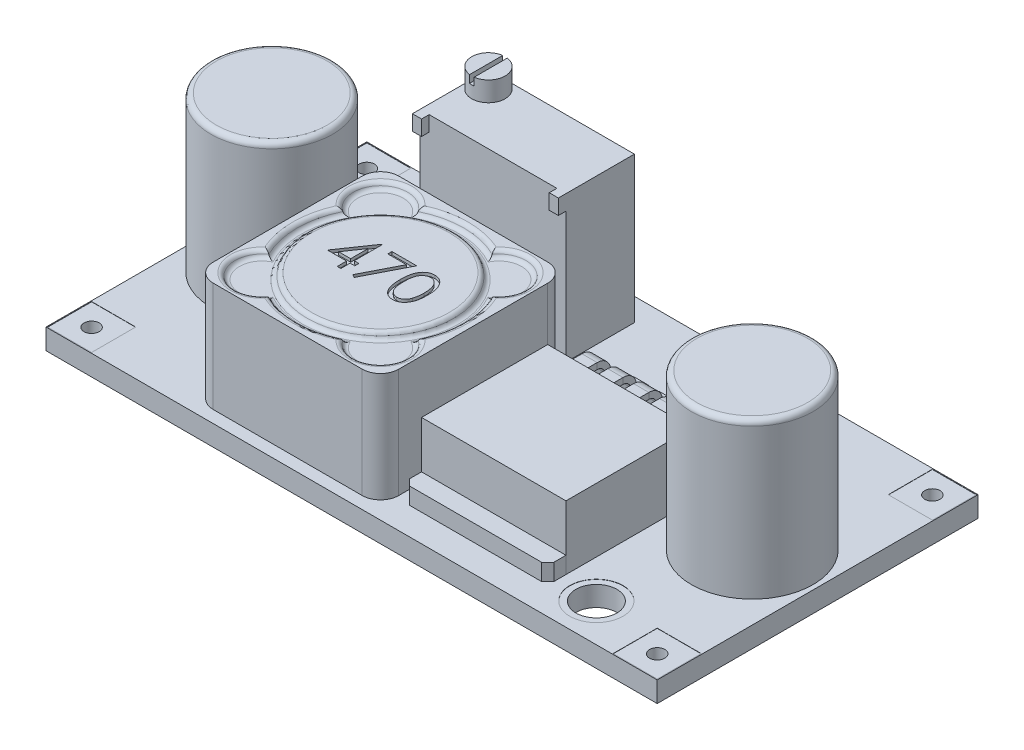
SolidWorks part; units mm, degrees
ref_plane "Front Plane" through (0, 0, 0) normal (0, 0, 1) x (1, 0, 0)
ref_plane "Top Plane" through (0, 0, 0) normal (0, 1, 0) x (1, 0, 0)
ref_plane "Right Plane" through (0, 0, 0) normal (1, 0, 0) x (0, 0, -1)
sketch "Sketch1" plane through (0, 0, 0) normal (0, 1, 0) x (1, 0, 0)
  line L0 (-20.1, 10.55) -> (-18.6, 9.05) construction
  line L1 (-20.1, -10.55) -> (20.1, -10.55)
  line L2 (-20.1, -10.55) -> (-20.1, 10.55)
  line L3 (-20.1, 10.55) -> (20.1, 10.55)
  line L4 (20.1, -10.55) -> (20.1, 10.55)
  line L5 (-20.1, -10.55) -> (20.1, 10.55) construction
  line L6 (-20.1, 10.55) -> (20.1, -10.55) construction
  line L7 (0, 0) -> (0, 10.55) construction
  line L8 (0, 0) -> (-20.1, 0) construction
  line L9 (-13.6, 8.05) -> (-13.6, 10.55) construction
  line L10 (-13.6, 8.05) -> (-20.1, 8.05) construction
  line L11 (20.1, -8.05) -> (13.6, -8.05) construction
  line L12 (13.6, -8.05) -> (13.6, -10.55) construction
  circle A0 centre (-18.6, 9.05) radius 0.5
  circle A1 centre (18.6, 9.05) radius 0.5
  circle A2 centre (18.6, -9.05) radius 0.5
  circle A3 centre (-18.6, -9.05) radius 0.5
  circle A4 centre (-13.6, 8.05) radius 1.35
  circle A5 centre (13.6, -8.05) radius 1.35
  point P0 (0, 0)
  dimension "D5" = 1
  dimension "D6" = 2.7
  dimension "D1" = 21.1
  dimension "D2" = 40.2
  dimension "D3" = 45
  dimension "D4" = 1.5
  dimension "D7" = 6.5
  dimension "D8" = 2.5
extrude "Boss-Extrude1" add sketch "Sketch1" along normal blind 1.35
sketch "Sketch3" plane through (0, 1.35, 0) normal (0, 1, 0) x (1, 0, 0)
  line L1 (-20.1, 10.55) -> (-20.1, -10.55) construction
  circle A0 centre (-15.8, 0) radius 4
  dimension "D1" = 4.3
  dimension "D2" = 8
extrude "Boss-Extrude2" add sketch "Sketch3" along normal blind 10.2
mirror "Mirror6" about plane through (0, 0, 0) normal (1, 0, 0) of "Boss-Extrude2"
sketch "Sketch4" plane through (0, 1.35, 0) normal (0, 1, 0) x (1, 0, 0)
  line L0 (20.1, 10.55) -> (-20.1, 10.55) construction
  line L1 (-10.6, 9.05) -> (-1, 9.05)
  line L2 (-10.6, 9.05) -> (-10.6, 4.55)
  line L3 (-10.6, 4.55) -> (-1, 4.55)
  line L4 (-1, 9.05) -> (-1, 4.55)
  line L5 (-20.1, 10.55) -> (-20.1, -10.55) construction
  dimension "D1" = 4.5
  dimension "D2" = 9.6
  dimension "D3" = 1.5
  dimension "D4" = 9.5
extrude "Boss-Extrude3" add sketch "Sketch4" along normal blind 9.6
sketch "Sketch5" plane through (0, 1.35, 0) normal (0, 1, 0) x (1, 0, 0)
  line L0 (-20.1, -10.55) -> (20.1, -10.55) construction
  line L1 (-9.9, 2.45) -> (-0.1, 2.45)
  line L2 (-11.1, 1.25) -> (-11.1, -8.55)
  line L3 (-9.9, -9.75) -> (-0.1, -9.75)
  line L4 (1.1, 1.25) -> (1.1, -8.55)
  line L5 (-20.1, 10.55) -> (-20.1, -10.55) construction
  arc A0 (-0.1, 2.45) -> (1.1, 1.25) centre (-0.1, 1.25) cw
  arc A1 (-0.1, -9.75) -> (1.1, -8.55) centre (-0.1, -8.55) ccw
  arc A2 (-11.1, -8.55) -> (-9.9, -9.75) centre (-9.9, -8.55) ccw
  arc A3 (-9.9, 2.45) -> (-11.1, 1.25) centre (-9.9, 1.25) ccw
  point P10 (1.1, 2.45)
  point P15 (-11.1, -9.75)
  point P18 (-11.1, 2.45)
  dimension "D5" = 1.2
  dimension "D1" = 12.2
  dimension "D2" = 12.2
  dimension "D3" = 0.8
  dimension "D4" = 9
extrude "Boss-Extrude4" add sketch "Sketch5" along normal blind 7.2
sketch "Sketch6" plane through (0, 1.35, 0) normal (0, 1, 0) x (1, 0, 0)
  line L0 (1.1, -8.55) -> (1.1, 1.25) construction
  line L1 (1.6, -7.55) -> (11.1, -7.55)
  line L2 (1.6, -7.55) -> (1.6, 0.75)
  line L3 (1.6, 0.75) -> (11.1, 0.75)
  line L4 (11.1, -7.55) -> (11.1, 0.75)
  line L5 (-20.1, -10.55) -> (20.1, -10.55) construction
  dimension "D1" = 9.5
  dimension "D2" = 0.5
  dimension "D3" = 8.3
  dimension "D4" = 3
extrude "Boss-Extrude5" add sketch "Sketch6" along normal blind 4.2
sketch "Sketch7" plane through (0, 1.35, 0) normal (0, 1, 0) x (1, 0, 0)
  line L1 (-20.05, 7.6) -> (-17.15, 7.6)
  line L2 (-20.05, 7.6) -> (-20.05, 10.5)
  line L3 (-20.05, 10.5) -> (-17.15, 10.5)
  line L4 (-17.15, 7.6) -> (-17.15, 10.5)
  line L5 (-20.05, 7.6) -> (-17.15, 10.5) construction
  line L6 (-20.05, 10.5) -> (-17.15, 7.6) construction
  circle A0 centre (-18.6, 9.05) radius 0.5 construction
  circle A1 centre (-18.6, 9.05) radius 0.5
  point P0 (-18.6, 9.05)
  dimension "D1" = 2.9
extrude "Cut-Extrude1" cut sketch "Sketch7" against normal blind 0.015
ref_plane "Plane1" through (0, 0.675, 0) normal (0, 1, 0) x (1, 0, 0)
mirror "Mirror7" about plane through (0, 0, 0) normal (1, 0, 0) of "Cut-Extrude1"
mirror "Mirror8" about plane through (0, 0, 0) normal (0, 0, 1) of "Mirror7", "Cut-Extrude1"
mirror "Mirror9" about plane through (0, 0.675, 0) normal (0, 1, 0) of "Mirror8", "Cut-Extrude1", "Mirror7"
sketch "Sketch8" plane through (0, 10.95, 0) normal (0, 1, 0) x (1, 0, 0)
  line L0 (-1, 9.05) -> (-10.6, 9.05) construction
  line L1 (-10.6, 9.05) -> (-10.6, 4.55) construction
  circle A0 centre (-9.5, 7.95) radius 1.1
  dimension "D1" = 2.2
extrude "Boss-Extrude6" add sketch "Sketch8" along normal blind 1.3 separate body
sketch "Sketch10" plane through (0, 8.55, 0) normal (0, 1, 0) x (1, 0, 0)
  line L0 (-11.1, -3.65) -> (1.1, -3.65) construction
  line L1 (-11.1, 1.25) -> (-11.1, -8.55) construction
  line L2 (1.1, -8.55) -> (1.1, 1.25) construction
  line L3 (-5, -9.75) -> (-5, 2.45) construction
  line L4 (-9.9, -9.75) -> (-0.1, -9.75) construction
  line L5 (-0.1, 2.45) -> (-9.9, 2.45) construction
  line L6 (-5, -3.65) -> (-8.8891, 0.2391) construction
  circle A0 centre (-5, -3.65) radius 4.8
  arc A1 (-9.9364, -1.2248) -> (-9.9364, -6.0752) centre (-5, -3.65) ccw
  arc A2 (-7.4252, 1.2864) -> (-9.9364, -1.2248) centre (-8.8891, 0.2391) ccw
  circle A3 centre (-5, -3.65) radius 5.5 construction
  arc A4 (-2.5748, 1.2864) -> (-0.0636, -1.2248) centre (-1.1109, 0.2391) cw
  arc A5 (-2.5748, -8.5864) -> (-0.0636, -6.0752) centre (-1.1109, -7.5391) ccw
  arc A6 (-7.4252, -8.5864) -> (-9.9364, -6.0752) centre (-8.8891, -7.5391) cw
  arc A7 (-2.5748, 1.2864) -> (-7.4252, 1.2864) centre (-5, -3.65) ccw
  arc A8 (-0.0636, -6.0752) -> (-0.0636, -1.2248) centre (-5, -3.65) ccw
  arc A9 (-7.4252, -8.5864) -> (-2.5748, -8.5864) centre (-5, -3.65) ccw
  dimension "D1" = 9.6
  dimension "D3" = 3.6
  dimension "D2" = 0.7
extrude "Cut-Extrude3" cut sketch "Sketch10" against normal blind 0.4
sketch "Sketch9" plane through (0, 12.25, 0) normal (0, 1, 0) x (1, 0, 0)
  line L0 (-9.5, 9.05) -> (-9.5, 6.85) construction
  line L1 (-1, 9.05) -> (-10.6, 9.05) construction
  line L2 (-1, 9.05) -> (-10.6, 9.05) construction
  line L3 (-9.65, 9.0397) -> (-9.65, 6.8603)
  line L4 (-9.35, 9.0397) -> (-9.35, 6.8603)
  line L5 (-9.65, 9.05) -> (-9.65, 6.85) construction
  line L6 (-9.35, 9.05) -> (-9.35, 6.85) construction
  circle A0 centre (-9.5, 7.95) radius 1.1 construction
  arc A1 (-9.35, 9.0397) -> (-9.65, 9.0397) centre (-9.5, 7.95) ccw
  arc A2 (-9.65, 6.8603) -> (-9.35, 6.8603) centre (-9.5, 7.95) ccw
  dimension "D1" = 0.15
  dimension "D2" = 0.15
extrude "Cut-Extrude2" cut sketch "Sketch9" against normal blind 0.5
fillet "Fillet2" radius 0.3 9 edges at (-5, 8.15, -1.85) (0.1619, 8.15, -1.5119) (0.5, 8.15, 3.65) (0.1619, 8.15, 8.8119) (-5, 8.15, 9.15) (-10.1619, 8.15, 8.8119) (-10.5, 8.15, 3.65) (-10.1619, 8.15, -1.5119) (-5, 8.15, 8.45)
fillet "Fillet3" radius 0.3 9 edges at (-10.1619, 8.55, -1.5119) (-10.5, 8.55, 3.65) (-10.1619, 8.55, 8.8119) (-5, 8.55, 9.15) (0.1619, 8.55, 8.8119) (0.5, 8.55, 3.65) (0.1619, 8.55, -1.5119) (-5, 8.55, -1.85) (-5, 8.55, 8.45)
sketch "Sketch11" plane through (0, 8.55, 0) normal (0, 1, 0) x (1, 0, 0)
  text T0 "470" font "Century Gothic" height in points 10
extrude "Cut-Extrude4" cut sketch "Sketch11" against normal blind 0.2
sketch "Sketch13" plane through (0, 0, -4.55) normal (0, 0, 1) x (1, 0, 0)
  line L0 (-5.8, 10.95) -> (-5.8, 9.4209) construction
  line L1 (-10.6, 10.95) -> (-10, 10.95)
  line L2 (-10.6, 10.95) -> (-10.6, 9.95)
  line L3 (-10.6, 9.95) -> (-10, 9.95)
  line L4 (-10, 10.95) -> (-10, 9.95)
  line L5 (-10.6, 10.95) -> (-1, 10.95) construction
  line L6 (-1, 9.95) -> (-1.6, 9.95)
  line L7 (-1.6, 10.95) -> (-1.6, 9.95)
  line L8 (-1, 10.95) -> (-1.6, 10.95)
  line L9 (-1, 10.95) -> (-1, 9.95)
  dimension "D1" = 1
  dimension "D2" = 0.6
extrude "Boss-Extrude7" add sketch "Sketch13" along normal blind 0.5
sketch "Sketch14" plane through (0, 1.35, 0) normal (0, 1, 0) x (1, 0, 0)
  line L0 (11.1, -7.55) -> (11.1, 0.75) construction
  line L1 (1.6, -7.55) -> (11.1, -7.55)
  line L2 (1.6, -7.55) -> (1.6, -8.35)
  line L3 (2, -8.75) -> (10.7, -8.75)
  line L4 (11.1, -7.55) -> (11.1, -8.35)
  line L5 (1.6, -8.35) -> (2, -8.75)
  line L6 (10.7, -8.75) -> (11.1, -8.35)
  point P1 (11.1, -8.75)
  point P2 (1.6, -8.75)
  dimension "D1" = 0.4
  dimension "D2" = 0.4
  dimension "D3" = 0.4
  dimension "D4" = 0.4
  dimension "D5" = 1.2
extrude "Boss-Extrude8" add sketch "Sketch14" along normal blind 1.1 separate body
sketch "Sketch16" plane through (0, 1.35, 0) normal (0, 1, 0) x (1, 0, 0)
  circle A0 centre (-13.6, 8.05) radius 1.35 construction
  circle A1 centre (-13.6, 8.05) radius 1.35
  circle A2 centre (13.6, -8.05) radius 1.35 construction
  circle A3 centre (13.6, -8.05) radius 1.35
  circle A4 centre (13.6, -8.05) radius 1.75
  circle A5 centre (-13.6, 8.05) radius 1.75
  dimension "D1" = 0.4
extrude "Cut-Extrude5" cut sketch "Sketch16" against normal blind 0.015
mirror "Mirror10" about plane through (0, 0.675, 0) normal (0, 1, 0) of "Cut-Extrude5"
ref_plane "Plane2" through (6.35, 0, 0) normal (1, 0, 0) x (0, 0, -1)
sketch "Sketch19" plane through (6.35, 0, 0) normal (1, 0, 0) x (0, 0, -1)
  line L0 (0.75, 4.55) -> (2.15, 4.55)
  line L2 (2.8396, 3.9702) -> (3.1604, 2.1298)
  line L3 (3.85, 1.55) -> (5.55, 1.55)
  line L5 (0.75, 5.55) -> (0.75, 1.35) construction
  line L6 (-7.55, 5.55) -> (0.75, 5.55) construction
  line L7 (-10.55, 1.35) -> (10.55, 1.35) construction
  arc A0 (3.1604, 2.1298) -> (3.85, 1.55) centre (3.85, 2.25) ccw
  arc A1 (2.15, 4.55) -> (2.8396, 3.9702) centre (2.15, 3.85) cw
  dimension "D1" = 4.8
  dimension "D3" = 0.7
  dimension "D2" = 1
  dimension "D4" = 1.7
  dimension "D5" = 1.7
  dimension "D6" = 0.2
sketch "Sketch20" plane through (0, 0, -0.75) normal (0, 0, -1) x (-1, 0, 0)
  line L0 (-6.35, 4.55) -> (-6.35, 3.9702) construction
  line L1 (-6.85, 4.35) -> (-5.85, 4.35)
  line L2 (-6.85, 4.35) -> (-6.85, 4.75)
  line L3 (-6.85, 4.75) -> (-5.85, 4.75)
  line L4 (-5.85, 4.35) -> (-5.85, 4.75)
  line L5 (-6.85, 4.35) -> (-5.85, 4.75) construction
  line L6 (-6.85, 4.75) -> (-5.85, 4.35) construction
  point P0 (-6.35, 4.55)
  dimension "D1" = 0.4
  dimension "D2" = 1
sweep "Sweep1" add profiles "Sketch20" path "Sketch19"
pattern_linear "LPattern1" count 3 spacing 1.7 along (-1, 0, 0) of "Sweep1"
pattern_linear "LPattern2" count 3 spacing 1.7 along (1, 0, 0) of "Sweep1"
sketch "Sketch21" plane through (0, 1.35, 0) normal (0, 1, 0) x (1, 0, 0)
  line L0 (20.1, 10.55) -> (-20.1, 10.55) construction
  line L1 (5.7, 9.35) -> (9.8, 9.35)
  line L2 (5.7, 9.35) -> (5.7, 6.75)
  line L3 (5.7, 6.75) -> (9.8, 6.75)
  line L4 (9.8, 9.35) -> (9.8, 6.75)
  line L5 (5.7, 9.35) -> (9.8, 6.75) construction
  line L6 (5.7, 6.75) -> (9.8, 9.35) construction
  line L7 (20.1, -10.55) -> (20.1, 10.55) construction
  point P0 (7.75, 8.05)
  dimension "D1" = 4.1
  dimension "D2" = 2.6
  dimension "D3" = 1.2
  dimension "D4" = 10.3
extrude "Boss-Extrude9" add sketch "Sketch21" along normal blind 1.6
sketch "Sketch22" plane through (0, 1.35, 0) normal (0, 1, 0) x (1, 0, 0)
  line L0 (7.75, 9.35) -> (7.75, 6.75) construction
  line L2 (5.7, 8.05) -> (5.3, 8.05) construction
  line L3 (5.7, 9.35) -> (5.7, 6.75) construction
  line L4 (9.8, 9.35) -> (5.7, 9.35) construction
  line L5 (5.3, 7.55) -> (5.7, 7.55)
  line L6 (5.3, 7.55) -> (5.3, 8.55)
  line L7 (5.3, 8.55) -> (5.7, 8.55)
  line L8 (5.7, 7.55) -> (5.7, 8.55)
  line L9 (5.3, 7.55) -> (5.7, 8.55) construction
  line L10 (5.3, 8.55) -> (5.7, 7.55) construction
  line L11 (5.7, 6.75) -> (9.8, 6.75) construction
  line L12 (10.2, 8.55) -> (9.8, 8.55)
  line L13 (9.8, 7.55) -> (9.8, 8.55)
  line L14 (10.2, 7.55) -> (9.8, 7.55)
  line L15 (10.2, 7.55) -> (10.2, 8.55)
  point P8 (5.5, 8.05)
  dimension "D1" = 0.4
  dimension "D2" = 1
extrude "Boss-Extrude10" add sketch "Sketch22" along normal offset from surface (1.1 mm away) 0.5 up to face at (7.75, 2.95, -8.05)
fillet "Fillet5" radius 0.5 2 edges at (10.2, 2.45, -8.05) (5.3, 2.45, -8.05)
fillet "Fillet6" radius 0.35 2 edges at (15.8, 11.55, 4) (-15.8, 11.55, 4)
sketch "Sketch23" plane through (0, 0, 0) normal (0, -1, 0) x (1, 0, 0)
  line L0 (-19.726, 5.6649) -> (-19.726, -6.4517) construction
  line L1 (-19.726, -0.3934) -> (18.9878, -0.3934) construction
  text T0 "IN+" font "Century Gothic" height in points 5
  text T1 "IN-" font "Century Gothic" height in points 5
sketch "Sketch24" plane through (0, 0, 0) normal (0, -1, 0) x (1, 0, 0)
  line L0 (15.4223, 5.6649) -> (15.4223, -6.4517) construction
  line L1 (-19.726, -0.3934) -> (18.9878, -0.3934) construction
  text T0 "OUT+" font "Century Gothic" height in points 5
  text T1 "OUT-" font "Century Gothic" height in points 5
  point P1 (15.4223, -0.3934)
extrude "Cut-Extrude6" cut sketch "Sketch23" against normal blind 0.015
extrude "Cut-Extrude7" cut sketch "Sketch24" against normal blind 0.015
sketch "Sketch25" plane through (0, 0, -9.05) normal (0, 0, -1) x (-1, 0, 0)
  text T0 "BONENS" font "Copperplate Gothic Light" height in points 5
  text T1 "3298" font "Copperplate Gothic Light" height in points 6
extrude "Cut-Extrude8" cut sketch "Sketch25" against normal blind 0.8
